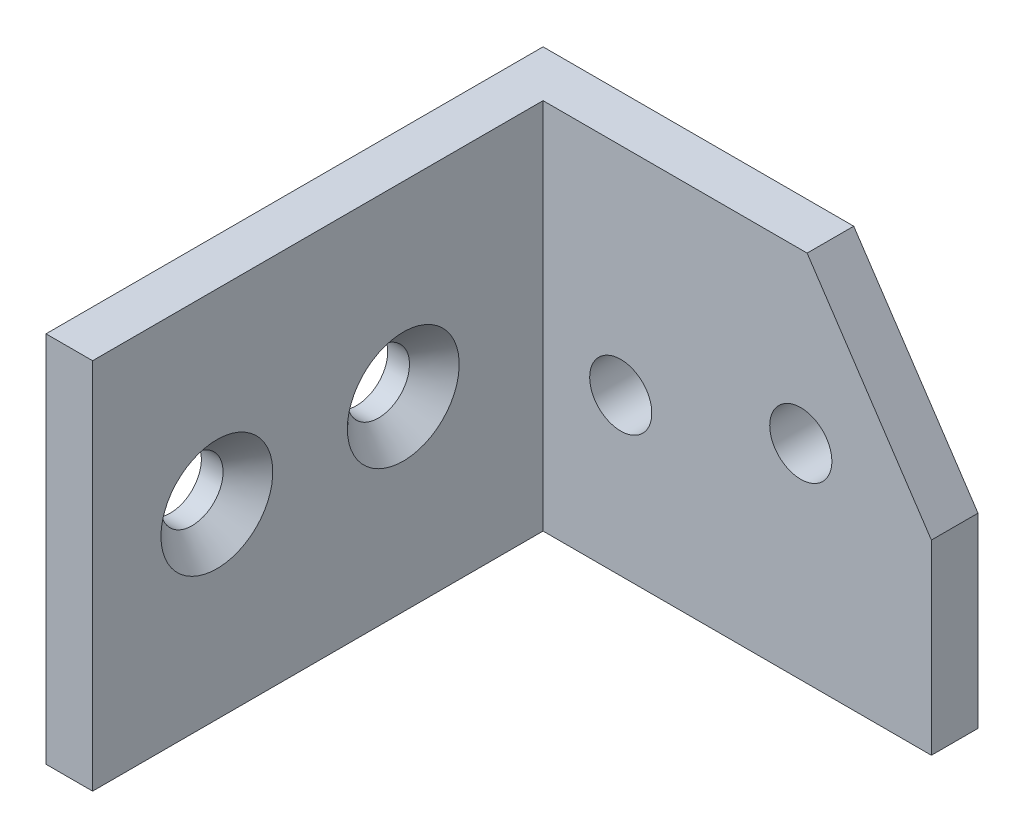
SolidWorks part; units mm, degrees
material "6061 Alloy"
ref_plane "Front Plane" through (0, 0, 0) normal (0, 0, 1) x (1, 0, 0)
ref_plane "Top Plane" through (0, 0, 0) normal (0, 1, 0) x (1, 0, 0)
ref_plane "Right Plane" through (0, 0, 0) normal (1, 0, 0) x (0, 0, -1)
sketch "Sketch1" plane through (0, 0, 0) normal (0, 1, 0) x (1, 0, 0)
  line L0 (0, 0) -> (0, 46.0375)
  line L1 (0, 46.0375) -> (39.6875, 46.0375)
  line L2 (39.6875, 46.0375) -> (39.6875, 50.8)
  line L3 (39.6875, 50.8) -> (-4.7625, 50.8)
  line L4 (-4.7625, 50.8) -> (-4.7625, 0)
  line L5 (-4.7625, 0) -> (0, 0)
  dimension "D1" = 44.45
  dimension "D2" = 50.8
  dimension "D3" = 4.7625
  dimension "D4" = 4.7625
extrude "Boss-Extrude1" add sketch "Sketch1" along normal blind 38.1
sketch "Sketch2" plane through (0, 0, -50.8) normal (0, 0, -1) x (-1, 0, 0)
  line L2 (-39.6875, 24.5038) -> (4.7625, 12.5935) construction
  line L3 (-39.6875, 38.1) -> (-39.6875, 0) construction
  line L4 (4.7625, 38.1) -> (4.7625, 0) construction
  line L5 (-39.6875, 38.1) -> (4.7625, 38.1) construction
  circle A0 centre (-26.3384, 20.9269) radius 3.175
  circle A1 centre (-7.9375, 15.9964) radius 3.175
  dimension "D1" = 6.35
  dimension "D2" = 15
  dimension "D3" = 0
  dimension "D4" = 19.05
  dimension "D7" = 6.35
  dimension "D6" = 12.7
  dimension "D5" = 0
extrude "Cut-Extrude1" cut sketch "Sketch2" against normal blind 38.1
sketch "Sketch3" plane through (-4.7625, 0, 0) normal (-1, 0, 0) x (0, 0, 1)
  line L2 (-50.8, 0) -> (0, 0) construction
  line L3 (0, 38.1) -> (0, 0) construction
  circle A0 centre (-12.7, 19.05) radius 3.175
  circle A1 centre (-31.75, 19.05) radius 3.175
  dimension "D1" = 6.35
  dimension "D2" = 6.35
  dimension "D3" = 19.05
  dimension "D4" = 19.05
  dimension "D5" = 12.7
  dimension "D6" = 19.05
extrude "Cut-Extrude3" cut sketch "Sketch3" against normal up to next
sketch "Sketch4" plane through (0, 0, -50.8) normal (0, 0, -1) x (-1, 0, 0)
  line L0 (-26.9875, 38.1) -> (-39.6875, 19.05)
  line L3 (-39.6875, 38.1) -> (4.7625, 38.1) construction
  line L4 (-39.6875, 38.1) -> (-39.6875, 0) construction
  dimension "D1" = 12.7
  dimension "D2" = 19.05
extrude "Cut-Extrude4" cut sketch "Sketch4" against normal through all and the other way through all flip side to cut contours L0
chamfer "Chamfer1" distance 2.54 angle 45 2 edges at (0, 19.05, -9.525) (0, 19.05, -28.575)
